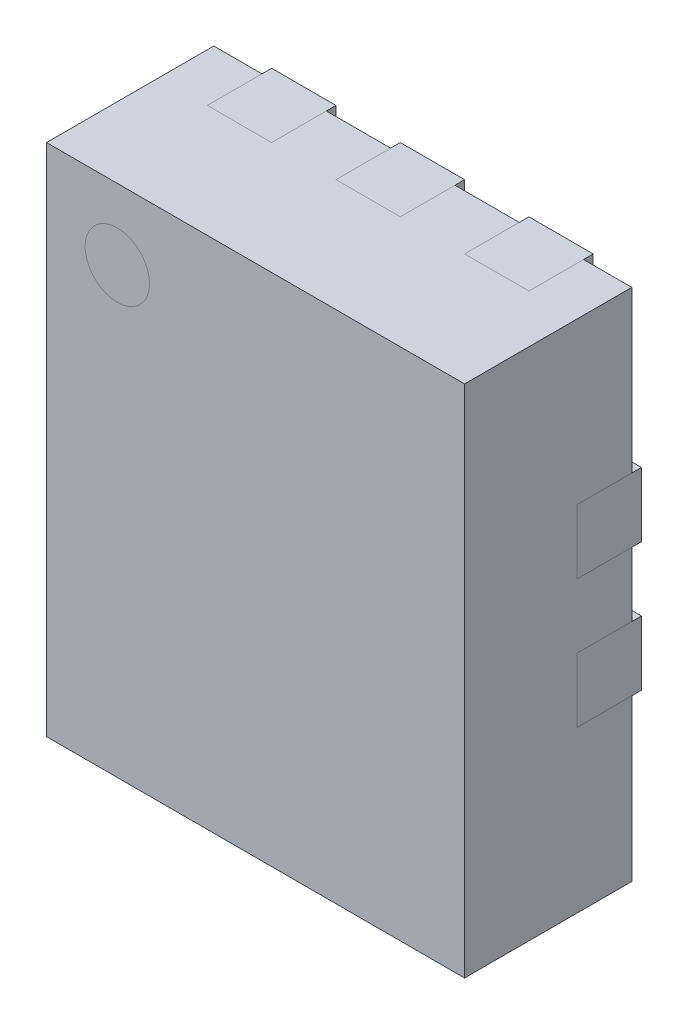
SolidWorks part; units mm, degrees
ref_plane "Спереди" through (0, 0, 0) normal (0, 0, 1) x (1, 0, 0)
ref_plane "Сверху" through (0, 0, 0) normal (0, 1, 0) x (1, 0, 0)
ref_plane "Справа" through (0, 0, 0) normal (1, 0, 0) x (0, 0, -1)
sketch "Эскиз1" plane through (0, 0, 0) normal (0, 0, 1) x (1, 0, 0)
  line L1 (-0.65, -0.8) -> (0.65, -0.8)
  line L2 (-0.65, -0.8) -> (-0.65, 0.8)
  line L3 (-0.65, 0.8) -> (0.65, 0.8)
  line L4 (0.65, -0.8) -> (0.65, 0.8)
  line L5 (-0.65, -0.8) -> (0.65, 0.8) construction
  line L6 (-0.65, 0.8) -> (0.65, -0.8) construction
  point P0 (0, 0)
  dimension "D1" = 1.3
  dimension "D2" = 1.6
extrude "Вытянуть1" add sketch "Эскиз1" along normal blind 0.52 from offset 0.03
sketch "Эскиз2" plane through (0, 0, 0.55) normal (0, 0, 1) x (1, 0, 0)
  line L0 (-0.65, 0.8) -> (-0.65, -0.8) construction
  line L1 (0.65, 0.8) -> (-0.65, 0.8) construction
  circle A0 centre (-0.43, 0.58) radius 0.1
  dimension "D1" = 0.2
  dimension "D2" = 0.22
  dimension "D3" = 0.22
extrude "Вырез-Вытянуть1" cut sketch "Эскиз2" against normal blind 0.05
extrude "Бобышка-Вытянуть1" add sketch "Эскиз2<2>" against normal blind 0.05 separate body
sketch "Эскиз2<2>" plane through (0, 0, 0.55) normal (0, 0, 1) x (1, 0, 0) same geometry as "Эскиз2"
sketch "Эскиз3" plane through (0, 0, 0) normal (0, 0, 1) x (1, 0, 0)
  line L0 (0, 0) -> (0, 0.8) construction
  line L1 (0.65, 0.8) -> (-0.65, 0.8) construction
  line L2 (0, 0) -> (0.65, 0) construction
  line L3 (0.65, -0.8) -> (0.65, 0.8) construction
  line L4 (-0.4, 0.8) -> (-0.4, -0.8) construction
  line L5 (-0.01, 0.5) -> (0.01, 0.5)
  line L6 (-0.1, 0.59) -> (-0.1, 0.8)
  line L7 (-0.1, 0.8) -> (0.1, 0.8)
  line L8 (0.1, 0.59) -> (0.1, 0.8)
  line L9 (-0.0996, 0.5005) -> (0.1, 0.8) construction
  line L10 (-0.1, 0.8) -> (0.1004, 0.4995) construction
  line L11 (0.5, 0.5) -> (0.3, 0.5) construction
  line L12 (-0.41, 0.5) -> (-0.39, 0.5) construction
  line L13 (-0.5, 0.59) -> (-0.5, 0.8) construction
  line L14 (-0.5, 0.8) -> (-0.3, 0.8) construction
  line L15 (-0.3, 0.59) -> (-0.3, 0.8) construction
  line L16 (0.4, 0.8) -> (0.4, 0.5) construction
  line L17 (-0.01, -0.5) -> (0.01, -0.5)
  line L18 (0.3, 0.5) -> (0.3, 0.8) construction
  line L19 (0.5, 0.8) -> (0.3, 0.8) construction
  line L20 (0.5, 0.5) -> (0.5, 0.8) construction
  line L21 (-0.65, -0.8) -> (0.65, -0.8) construction
  line L22 (0.1, -0.59) -> (0.1, -0.8)
  line L23 (-0.1, -0.8) -> (0.1, -0.8)
  line L24 (-0.1, -0.59) -> (-0.1, -0.8)
  line L25 (-0.41, -0.5) -> (-0.39, -0.5)
  line L26 (-0.3, -0.59) -> (-0.3, -0.8)
  line L27 (-0.5, -0.8) -> (-0.3, -0.8)
  line L28 (-0.5, -0.59) -> (-0.5, -0.8)
  line L29 (0.4, 0.5) -> (0.4, -0.8) construction
  line L30 (0.65, 0.2) -> (0.1453, 0.2) construction
  line L31 (0.3, -0.8) -> (0.5, -0.8)
  line L32 (0.3, -0.8) -> (0.3, -0.59)
  line L33 (0.39, -0.5) -> (0.41, -0.5)
  line L34 (0.5, -0.8) -> (0.5, -0.59)
  line L35 (0.3, -0.8) -> (0.4736, -0.5264) construction
  line L36 (0.3264, -0.5264) -> (0.5, -0.8) construction
  line L37 (0.65, -0.1) -> (0.65, -0.3)
  line L38 (0.34, 0.1) -> (0.65, 0.1)
  line L39 (0.25, 0.19) -> (0.25, 0.21)
  line L40 (0.34, 0.3) -> (0.65, 0.3)
  line L41 (0.65, 0.1) -> (0.65, 0.3)
  line L42 (0.2764, 0.1264) -> (0.65, 0.3) construction
  line L43 (0.2446, 0.2884) -> (0.65, 0.1) construction
  line L44 (0.34, -0.3) -> (0.65, -0.3)
  line L45 (0.25, -0.19) -> (0.25, -0.21)
  line L46 (0.34, -0.1) -> (0.65, -0.1)
  line L47 (-0.65, -0.1) -> (-0.65, -0.3)
  line L48 (-0.34, -0.3) -> (-0.65, -0.3)
  line L49 (-0.25, -0.19) -> (-0.25, -0.21)
  line L50 (-0.34, -0.1) -> (-0.65, -0.1)
  line L51 (-0.25, 0.19) -> (-0.25, 0.21)
  line L52 (-0.34, 0.3) -> (-0.65, 0.3)
  line L53 (-0.65, 0.1) -> (-0.65, 0.3)
  line L54 (-0.34, 0.1) -> (-0.65, 0.1)
  line L55 (0.3, 0.59) -> (0.3, 0.8)
  line L56 (0.5, 0.8) -> (0.3, 0.8)
  line L57 (0.5, 0.59) -> (0.5, 0.8)
  line L58 (0.41, 0.5) -> (0.39, 0.5)
  line L59 (-0.5, 0.8) -> (-0.3, 0.8)
  line L60 (-0.3, 0.8) -> (-0.3, 0.5)
  line L61 (-0.3, 0.5) -> (-0.5, 0.5)
  line L62 (-0.5, 0.5) -> (-0.5, 0.8)
  arc A0 (0.01, 0.5) -> (0.1, 0.59) centre (0.01, 0.59) ccw
  arc A1 (-0.01, 0.5) -> (-0.1, 0.59) centre (-0.01, 0.59) cw
  arc A2 (-0.39, 0.5) -> (-0.3, 0.59) centre (-0.39, 0.59) ccw construction
  arc A3 (-0.41, 0.5) -> (-0.5, 0.59) centre (-0.41, 0.59) cw construction
  arc A4 (-0.01, -0.5) -> (-0.1, -0.59) centre (-0.01, -0.59) ccw
  arc A5 (0.01, -0.5) -> (0.1, -0.59) centre (0.01, -0.59) cw
  arc A6 (-0.41, -0.5) -> (-0.5, -0.59) centre (-0.41, -0.59) ccw
  arc A7 (-0.39, -0.5) -> (-0.3, -0.59) centre (-0.39, -0.59) cw
  arc A8 (0.41, -0.5) -> (0.5, -0.59) centre (0.41, -0.59) cw
  arc A9 (0.39, -0.5) -> (0.3, -0.59) centre (0.39, -0.59) ccw
  arc A10 (0.25, -0.21) -> (0.34, -0.3) centre (0.34, -0.21) ccw
  arc A11 (0.34, -0.1) -> (0.25, -0.19) centre (0.34, -0.19) ccw
  arc A12 (0.25, 0.21) -> (0.34, 0.3) centre (0.34, 0.21) cw
  arc A13 (0.34, 0.1) -> (0.25, 0.19) centre (0.34, 0.19) cw
  arc A14 (-0.25, -0.21) -> (-0.34, -0.3) centre (-0.34, -0.21) cw
  arc A15 (-0.34, -0.1) -> (-0.25, -0.19) centre (-0.34, -0.19) cw
  arc A16 (-0.34, 0.1) -> (-0.25, 0.19) centre (-0.34, 0.19) ccw
  arc A17 (-0.25, 0.21) -> (-0.34, 0.3) centre (-0.34, 0.21) ccw
  arc A18 (0.41, 0.5) -> (0.5, 0.59) centre (0.41, 0.59) ccw
  arc A19 (0.39, 0.5) -> (0.3, 0.59) centre (0.39, 0.59) cw
  point P8 (0, 0.65)
  point P53 (0.4, -0.6424)
  point P67 (0.4348, 0.2)
  dimension "D6" = 0.09
  dimension "D13" = 0.09
  dimension "D20" = 0.09
  dimension "D1" = 0.2
  dimension "D2" = 0.3
  dimension "D3" = 0.4
  dimension "D4" = 0.2
  dimension "D5" = 0.3
  dimension "D7" = 0.2
  dimension "D8" = 0.3
  dimension "D9" = 0.15
  dimension "D10" = 0.1
  dimension "D11" = 0.3
  dimension "D12" = 0.2
  dimension "D14" = 0.1
  dimension "D15" = 0.2
  dimension "D16" = 0.2
  dimension "D17" = 0.4
  dimension "D23" = 0.1
extrude "Вырез-Вытянуть2" cut sketch "Эскиз3" along normal blind 0.2
extrude "Бобышка-Вытянуть2" add sketch "Эскиз3<2>" along normal blind 0.2 separate body
sketch "Эскиз3<2>" plane through (0, 0, 0) normal (0, 0, 1) x (1, 0, 0) same geometry as "Эскиз3"
